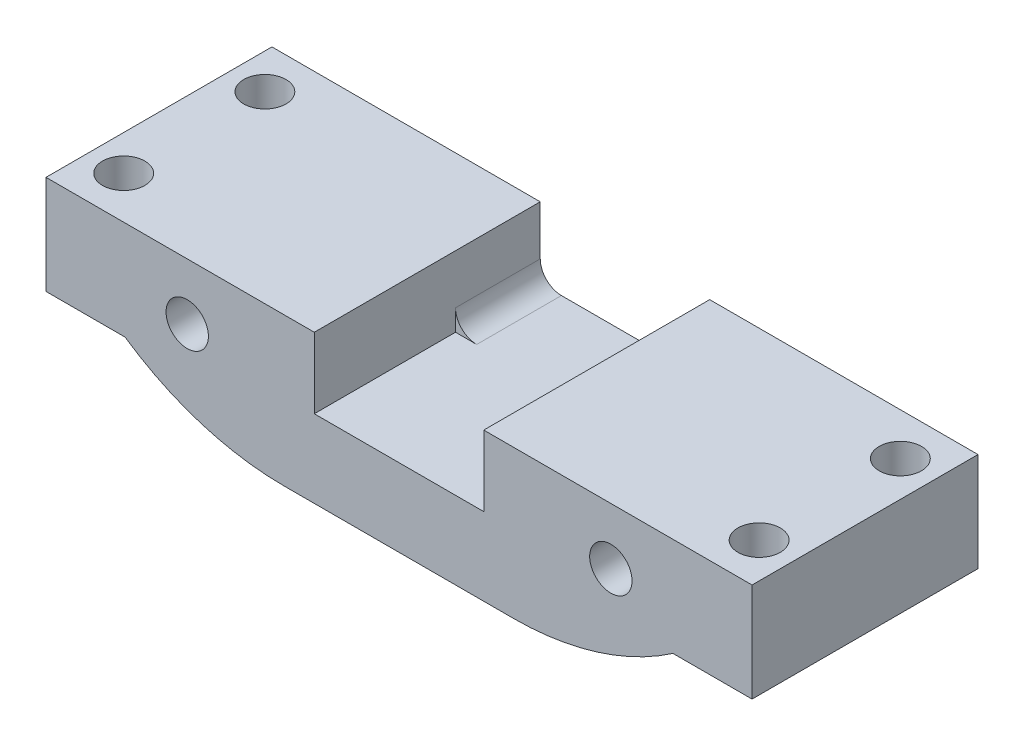
SolidWorks part; units mm, degrees
ref_plane "Front Plane" through (0, 0, 0) normal (0, 0, 1) x (1, 0, 0)
ref_plane "Top Plane" through (0, 0, 0) normal (0, 1, 0) x (1, 0, 0)
ref_plane "Right Plane" through (0, 0, 0) normal (1, 0, 0) x (0, 0, -1)
sketch "Sketch7" plane through (0, 0, 0) normal (0, 0, 1) x (1, 0, 0)
  line L20 (-2, 14.9) -> (11, 14.9)
  line L21 (35, 14.9) -> (48, 14.9)
  line L22 (11, 14.9) -> (17, 14.9)
  line L24 (3.5981, 7.9) -> (-2, 7.9)
  line L25 (3.5981, 7.9) -> (3.5981, 4.4)
  line L26 (42.4, 7.9) -> (42.4, 4.4)
  line L29 (48, 7.9) -> (42.4, 7.9)
  line L31 (48, 14.9) -> (48, 7.9)
  line L32 (-2, 14.9) -> (-2, 7.9)
  line L33 (3.5981, 4.4) -> (42.4, 4.4)
  line L35 (17, 14.9) -> (17, 9.9)
  line L36 (29, 14.9) -> (29, 9.9)
  line L37 (17, 9.9) -> (29, 9.9)
  line L38 (29, 14.9) -> (35, 14.9)
  circle A1 centre (8, 10.9) radius 1.5
  circle A2 centre (38, 10.9) radius 1.5
  dimension "D3" = 5.5981
  dimension "D4" = 13
  dimension "D10" = 12
  dimension "D11" = 3
  dimension "D12" = 5.6
  dimension "D13" = 19
  dimension "D15" = 3
  dimension "D7" = 13
  dimension "D8" = 4
  dimension "D2" = 5
  dimension "D16" = 10
  dimension "D5" = 13
  dimension "D6" = 10
  dimension "D9" = 4
  dimension "D14" = 7
extrude "Boss-Extrude11" add sketch "Sketch7" along normal blind 10 contours L20 L32 L24 L25 L26 L29 L31 L21 A2 A1 region at (22.9997, 9.5395, 0)
ref_plane "Plane2" through (0, 7.9, 0) normal (0, -1, 0) x (-1, 0, 0)
sketch "Sketch8" plane through (0, 7.9, 0) normal (0, -1, 0) x (1, 0, 0)
  line L8 (-2, 0) -> (17, 0) construction
  line L9 (-2, 10) -> (-2, 0) construction
  line L11 (-2, 10) -> (17, 10) construction
  line L12 (48, 10) -> (48, 0) construction
  line L13 (29, 0) -> (48, 0) construction
  line L14 (29, 10) -> (48, 10) construction
  circle A0 centre (0.5, 7) radius 1.5
  circle A1 centre (45.5, 7) radius 1.5
  circle A2 centre (45.5, 3) radius 1.5
  circle A3 centre (0.5, 3) radius 1.5
  dimension "D1" = 3
  dimension "D2" = 3
  dimension "D3" = 2.5
  dimension "D4" = 2.5
  dimension "D5" = 3
  dimension "D6" = 2.5
  dimension "D7" = 3
  dimension "D8" = 3
  dimension "D9" = 2.5
fillet "Fillet1" radius 20 2 edges at (42.4, 4.4, 5) (3.5981, 4.4, 5)
sketch "Sketch9" plane through (0, 0, 0) normal (0, 0, -1) x (-1, 0, 0)
  line L10 (-48, 7.9) -> (-42.4, 7.9)
  line L11 (-31.0973, 4.4) -> (-14.9007, 4.4)
  line L12 (-3.5981, 7.9) -> (2, 7.9)
  line L13 (2, 7.9) -> (2, 14.9)
  line L14 (2, 14.9) -> (-17, 14.9)
  line L15 (-17, 14.9) -> (-17, 9.9)
  line L16 (-17, 9.9) -> (-29, 9.9)
  line L17 (-29, 9.9) -> (-29, 14.9)
  line L18 (-29, 14.9) -> (-48, 14.9)
  line L19 (-48, 14.9) -> (-48, 7.9)
  line L20 (-48, 7.9) -> (-42.4, 7.9)
  line L21 (-31.0973, 4.4) -> (-14.9007, 4.4)
  line L22 (-3.5981, 7.9) -> (2, 7.9)
  line L23 (2, 7.9) -> (2, 14.9)
  line L24 (2, 14.9) -> (-17, 14.9)
  line L25 (-17, 14.9) -> (-17, 11.4)
  line L26 (-18.5, 9.9) -> (-27.5, 9.9)
  line L27 (-29, 11.4) -> (-29, 14.9)
  line L28 (-29, 14.9) -> (-48, 14.9)
  line L29 (-48, 14.9) -> (-48, 7.9)
  arc A0 (-18.5, 9.9) -> (-17, 11.4) centre (-18.5, 11.4) ccw
  arc A1 (-29, 11.4) -> (-27.5, 9.9) centre (-27.5, 11.4) ccw
  arc A2 (-42.4, 7.9) -> (-31.0973, 4.4) centre (-31.0973, 24.4) ccw
  arc A3 (-14.9007, 4.4) -> (-3.5981, 7.9) centre (-14.9007, 24.4) ccw
  arc A4 (-42.4, 7.9) -> (-31.0973, 4.4) centre (-31.0973, 24.4) ccw
  arc A5 (-14.9007, 4.4) -> (-3.5981, 7.9) centre (-14.9007, 24.4) ccw
  dimension "D2" = 3
  dimension "D1" = 0
extrude "Boss-Extrude12" add sketch "Sketch9" along normal blind 6
sketch "Sketch10" plane through (0, 14.9, 0) normal (0, 1, 0) x (1, 0, 0)
  line L0 (29, 6) -> (48, 6) construction
  line L2 (-2, -10) -> (-2, 6) construction
  line L3 (48, -10) -> (48, 6) construction
  line L4 (-2, 6) -> (17, 6) construction
  line L5 (-2, -10) -> (17, -10) construction
  line L6 (29, -10) -> (48, -10) construction
  circle A0 centre (0.5, -7) radius 1.5 construction
  circle A1 centre (0.5, -7) radius 1.5
  circle A2 centre (0.5, 3) radius 1.5
  circle A3 centre (45.5, -7) radius 1.5 construction
  circle A4 centre (45.5, -7) radius 1.5
  circle A5 centre (45.5, 3) radius 1.5
  dimension "D2" = 2.5
  dimension "D1" = 3
  dimension "D3" = 2.5
  dimension "D4" = 2.5
  dimension "D5" = 2.5
  dimension "D6" = 3
  dimension "D7" = 3
  dimension "D8" = 3
extrude "Cut-Extrude1" cut sketch "Sketch10" against normal through all both and the other way through all
